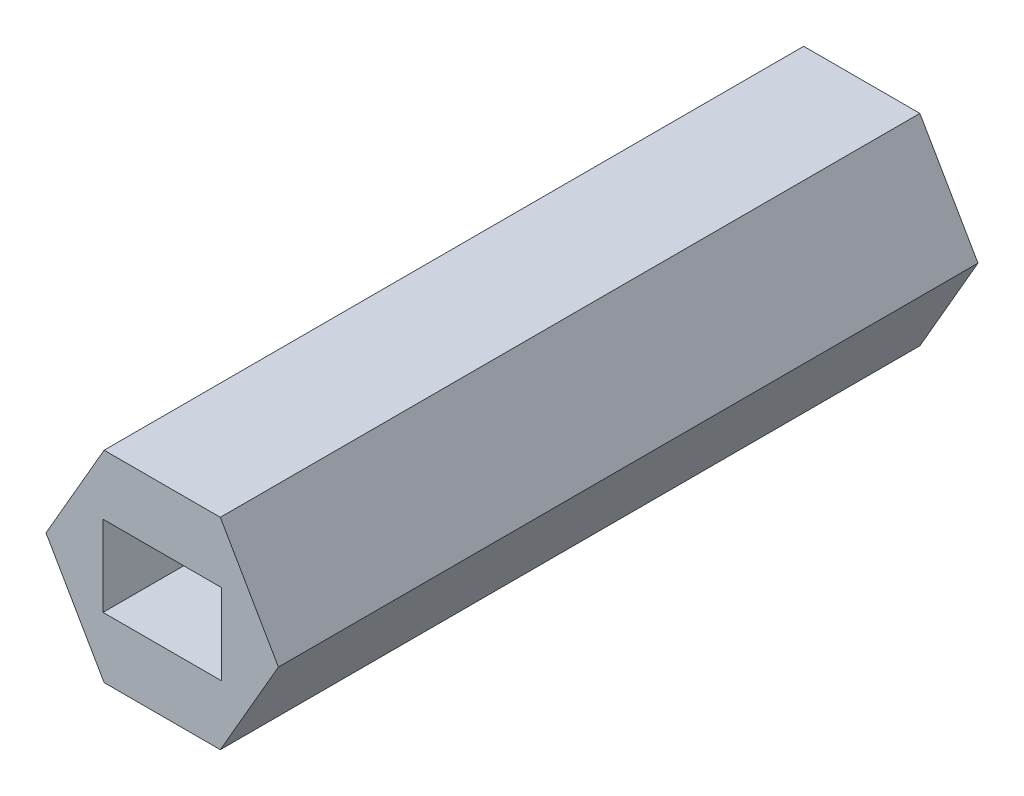
SolidWorks part; units mm, degrees
ref_plane "Front Plane" through (0, 0, 0) normal (0, 0, 1) x (1, 0, 0)
ref_plane "Top Plane" through (0, 0, 0) normal (0, 1, 0) x (1, 0, 0)
ref_plane "Right Plane" through (0, 0, 0) normal (1, 0, 0) x (0, 0, -1)
sketch "Sketch1" plane through (0, 0, 0) normal (0, 0, 1) x (1, 0, 0)
  line L1 (-2.7424, 4.75) -> (-5.4848, 0)
  line L2 (-5.4848, 0) -> (-2.7424, -4.75)
  line L3 (-2.7424, -4.75) -> (2.7424, -4.75)
  line L4 (2.7424, -4.75) -> (5.4848, 0)
  line L5 (5.4848, 0) -> (2.7424, 4.75)
  line L6 (2.7424, 4.75) -> (-2.7424, 4.75)
  line L7 (2.794, -1.905) -> (-2.794, -1.905)
  line L8 (2.794, -1.905) -> (2.794, 1.905)
  line L9 (2.794, 1.905) -> (-2.794, 1.905)
  line L10 (-2.794, -1.905) -> (-2.794, 1.905)
  line L11 (2.794, -1.905) -> (-2.794, 1.905) construction
  line L12 (2.794, 1.905) -> (-2.794, -1.905) construction
  circle A0 centre (0, 0) radius 4.75 construction
  dimension "D1" = 9.5
  dimension "D2" = 3.81
  dimension "D3" = 5.588
extrude "Boss-Extrude1" add sketch "Sketch1" along normal blind 33.02
